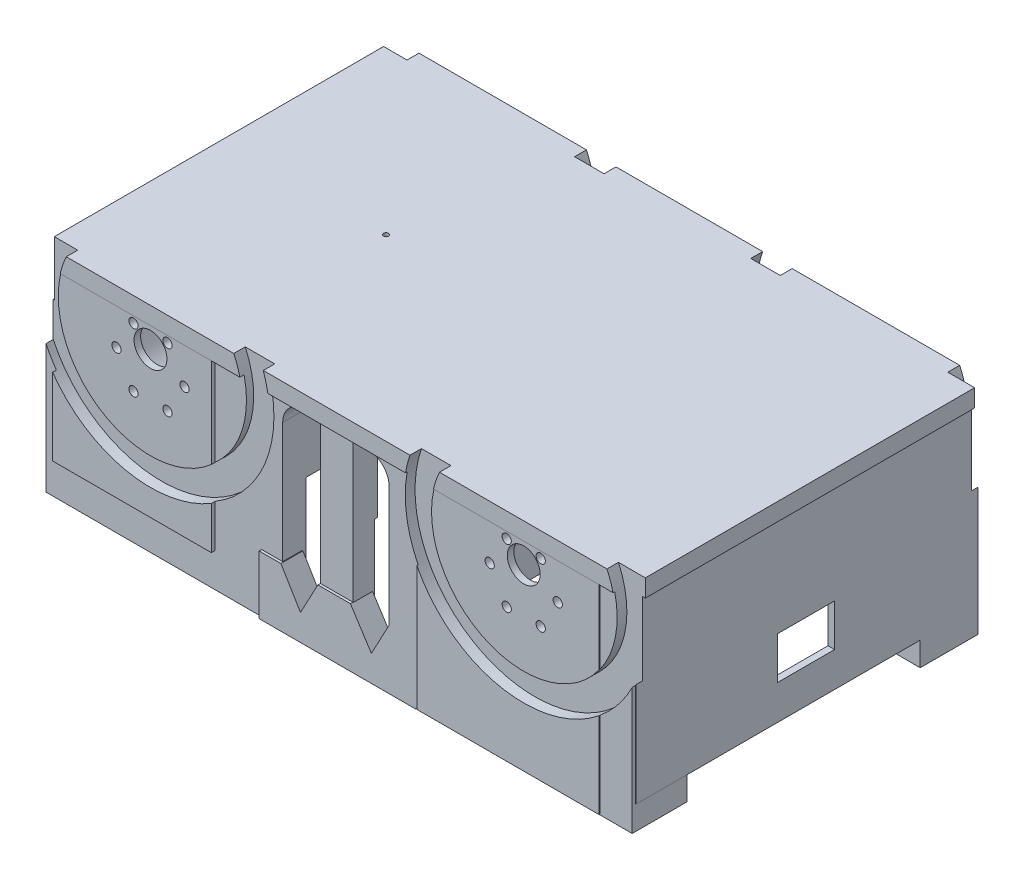
SolidWorks part; units mm, degrees
ref_plane "Front Plane" through (0, 0, 0) normal (0, 0, 1) x (1, 0, 0)
ref_plane "Top Plane" through (0, 0, 0) normal (0, 1, 0) x (1, 0, 0)
ref_plane "Right Plane" through (0, 0, 0) normal (1, 0, 0) x (0, 0, -1)
sketch "MotorHoldersSketch" plane through (0, 0, 0) normal (0, 0, 1) x (1, 0, 0)
  line L0 (0, 0) -> (170, 0) construction
  line L1 (0, 0) -> (0, 23.41) construction
  line L2 (170, 0) -> (170, 23.41) construction
  circle A0 centre (0, 0) radius 23.41
  circle A1 centre (170, 0) radius 23.41
ref_axis "MotorCenterAxis1" through (0, 0, 0) along (0, 0, 1)
ref_axis "MotorCenterAxis2" through (170, 0, 0) along (0, 0, 1)
extrude "MotorHolders" add sketch "MotorHoldersSketch" along normal blind 80 and the other way blind 80
sketch "Sketch3" plane through (0, 0, 0) normal (0, 0, 1) x (1, 0, 0)
  line L1 (1.9406, 21.133) -> (168.3435, 21.133)
  line L2 (1.9406, 21.133) -> (1.9406, 18.3155)
  line L3 (1.9406, 18.3155) -> (168.3435, 18.3155)
  line L4 (168.3435, 21.133) -> (168.3435, 18.3155)
sketch "Sketch4" plane through (0, 0, 0) normal (0, 1, 0) x (1, 0, 0)
  line L1 (221.2811, -76.3794) -> (-41.4939, -76.3794)
  line L2 (221.2811, -76.3794) -> (221.2811, 76.7331)
  line L3 (221.2811, 76.7331) -> (-41.4939, 76.7331)
  line L4 (-41.4939, -76.3794) -> (-41.4939, 76.7331)
extrude "Cut-Extrude1" cut sketch "Sketch4" against normal blind 26
ref_axis "Axis3" through (170, 0, 0) along (0, -1, 0)
sketch3d "ReferencePlanePosition"
  line L0 (170, 0, 0) -> (170, -34.8293, 0)
  line L1 (170, 0, 0) -> (170, -38.994, 0) construction
ref_plane "ReferencePlane" through (170, -34.8293, 0) normal (0, -1, 0) x (-1, 0, 0)
sketch "Sketch6" plane through (170, -34.8293, 0) normal (0, -1, 0) x (-1, 0, 0)
  line L1 (219.5858, 78.949) -> (112.1002, 78.949)
  line L2 (219.5858, 78.949) -> (219.5858, 65.5282)
  line L3 (219.5858, 65.5282) -> (112.1002, 65.5282)
  line L4 (112.1002, 78.949) -> (112.1002, 65.5282)
  line L5 (219.3147, -40.0209) -> (111.499, -40.0209)
  line L6 (219.3147, -40.0209) -> (219.3147, -78.2822)
  line L7 (219.3147, -78.2822) -> (111.499, -78.2822)
  line L8 (111.499, -40.0209) -> (111.499, -78.2822)
  line L9 (61.4891, 77.8627) -> (19.9904, 77.8627)
  line L10 (61.4891, 77.8627) -> (61.4891, 40.7512)
  line L11 (61.4891, 40.7512) -> (19.9904, 40.7512)
  line L12 (19.9904, 77.8627) -> (19.9904, 40.7512)
  line L13 (61.8484, -44.1716) -> (20.0852, -44.1716)
  line L14 (61.8484, -44.1716) -> (61.8484, -79.4437)
  line L15 (61.8484, -79.4437) -> (20.0852, -79.4437)
  line L16 (20.0852, -44.1716) -> (20.0852, -79.4437)
  line L17 (213.765, 73.0364) -> (192.9548, 73.0364)
  line L18 (213.765, 73.0364) -> (213.765, 71.0153)
  line L19 (213.765, 71.0153) -> (192.9548, 71.0153)
  line L20 (192.9548, 73.0364) -> (192.9548, 71.0153)
  line L21 (41.3552, 69.1777) -> (28.5109, 69.1777)
  line L22 (41.3552, 69.1777) -> (41.3552, 50.8413)
  line L23 (41.3552, 50.8413) -> (28.5109, 50.8413)
  line L24 (28.5109, 69.1777) -> (28.5109, 50.8413)
  line L25 (43.3068, -72.8101) -> (32.1723, -72.8101)
  line L26 (43.3068, -72.8101) -> (43.3068, -54.7747)
  line L27 (43.3068, -54.7747) -> (32.1723, -54.7747)
  line L28 (32.1723, -72.8101) -> (32.1723, -54.7747)
  line L29 (211.9411, -70.4881) -> (201.0982, -70.4881)
  line L30 (211.9411, -70.4881) -> (211.9411, -60.1404)
  line L31 (211.9411, -60.1404) -> (201.0982, -60.1404)
  line L32 (201.0982, -70.4881) -> (201.0982, -60.1404)
  line L33 (97.1795, 78.949) -> (79.4162, 78.949)
  line L34 (97.1795, 78.949) -> (97.1795, 67.7632)
  line L35 (97.1795, 67.7632) -> (79.4162, 67.7632)
  line L36 (79.4162, 78.949) -> (79.4162, 67.7632)
  line L37 (58.6711, 51.3198) -> (53.8697, 51.3198)
  line L38 (58.6711, 51.3198) -> (58.6711, 67.7632)
  line L39 (58.6711, 67.7632) -> (53.8697, 67.7632)
  line L40 (53.8697, 51.3198) -> (53.8697, 67.7632)
  line L41 (94.2281, -78.2822) -> (79.4162, -78.2822)
  line L42 (94.2281, -78.2822) -> (94.2281, -67.2515)
  line L43 (94.2281, -67.2515) -> (79.4162, -67.2515)
  line L44 (79.4162, -78.2822) -> (79.4162, -67.2515)
  line L45 (56.3648, -69.8638) -> (51.7107, -69.8638)
  line L46 (56.3648, -69.8638) -> (56.3648, -55.4273)
  line L47 (56.3648, -55.4273) -> (51.7107, -55.4273)
  line L48 (51.7107, -69.8638) -> (51.7107, -55.4273)
  line L49 (-20.7001, -79.4437) -> (-48.8506, -79.4437)
  line L50 (-20.7001, -79.4437) -> (-20.7001, -54.5097)
  line L51 (-20.7001, -54.5097) -> (-48.8506, -54.5097)
  line L52 (-48.8506, -79.4437) -> (-48.8506, -54.5097)
  line L53 (-18.3873, 77.8627) -> (-49.0581, 77.8627)
  line L54 (-18.3873, 77.8627) -> (-18.3873, 51.5325)
  line L55 (-18.3873, 51.5325) -> (-49.0581, 51.5325)
  line L56 (-49.0581, 77.8627) -> (-49.0581, 51.5325)
  line L57 (-41.8141, -72.8101) -> (-31.6362, -72.8101)
  line L58 (-41.8141, -72.8101) -> (-41.8141, -62.9794)
  line L59 (-41.8141, -62.9794) -> (-31.6362, -62.9794)
  line L60 (-31.6362, -72.8101) -> (-31.6362, -62.9794)
  line L61 (-31.6362, 69.1777) -> (-41.5347, 69.1777)
  line L62 (-31.6362, 69.1777) -> (-31.6362, 58.5421)
  line L63 (-31.6362, 58.5421) -> (-41.5347, 58.5421)
  line L64 (-41.5347, 69.1777) -> (-41.5347, 58.5421)
extrude "PowerBankHolders" add sketch "Sketch6" along normal blind 40 and the other way blind 59 separate body
sketch3d "3DSketch3"
  line L0 (170, 0, 0) -> (170, -64.5, 0) construction
ref_plane "Plane2" through (170, -64.5, 0) normal (0, -1, 0) x (-1, 0, 0)
sketch "Sketch7" plane through (170, -64.5, 0) normal (0, -1, 0) x (-1, 0, 0)
  line L1 (-9.5047, -80.801) -> (181.32, -80.801)
  line L2 (-9.5047, -80.801) -> (-9.5047, 73.8662)
  line L3 (-9.5047, 73.8662) -> (181.32, 73.8662)
  line L4 (181.32, -80.801) -> (181.32, 73.8662)
  line L5 (151.8712, -54.3972) -> (26.5361, -54.3972)
  line L6 (151.8712, -54.3972) -> (151.8712, 46.2413)
  line L7 (151.8712, 46.2413) -> (26.5361, 46.2413)
  line L8 (26.5361, -54.3972) -> (26.5361, 46.2413)
ref_point "Point1"
ref_point "Point2"
sketch3d "3DSketch11"
  line L0 (0, 0, -80) -> (170, 0, 80) construction
  point P4 (85, 0, 0)
sketch "MotorHolderExtrudeSketch" plane through (0, 0, 0) normal (0, 0, 1) x (1, 0, 0)
  circle A0 centre (170, 0) radius 20.415
  circle A1 centre (0, 0) radius 20.415
  circle A3 centre (0, 0) radius 23.41 construction
  circle A4 centre (170, 0) radius 23.41 construction
ref_point "TopOfMotors"
ref_plane "TangentToTopOfMotors" through (0, -20.415, 0) normal (0, 1, 0) x (1, 0, 0)
ref_axis "Axis4" through (85, 0, 0) along (0, -1, 0)
ref_plane "BottomOfPowerBankRegion" through (0, -20.425, 0) normal (0, 1, 0) x (1, 0, 0)
ref_point "CenterAtBottomOfPowerBank"
ref_plane "TopOfPowerBankPlane" through (0, -54.425, 0) normal (0, 1, 0) x (1, 0, 0)
sketch "Sketch13" plane through (0, -54.425, 0) normal (0, 1, 0) x (1, 0, 0)
  line L1 (-19.4498, 72.5454) -> (166.1636, 72.5454)
  line L2 (-19.4498, 72.5454) -> (-19.4498, -78.2051)
  line L3 (-19.4498, -78.2051) -> (166.1636, -78.2051)
  line L4 (166.1636, 72.5454) -> (166.1636, -78.2051)
  line L5 (19.3173, -49.583) -> (137.9607, -49.583)
  line L6 (19.3173, -49.583) -> (19.3173, -21.0549)
  line L7 (19.3173, -21.0549) -> (137.9607, -21.0549)
  line L8 (137.9607, -49.583) -> (137.9607, -21.0549)
  line L9 (19.3173, 56.6778) -> (137.9607, 56.6778)
  line L10 (19.3173, 56.6778) -> (19.3173, 36.3234)
  line L11 (19.3173, 36.3234) -> (137.9607, 36.3234)
  line L12 (137.9607, 56.6778) -> (137.9607, 36.3234)
  line L13 (19.3173, 18.3186) -> (137.9607, 18.3186)
  line L14 (19.3173, 18.3186) -> (19.3173, -7.3615)
  line L15 (19.3173, -7.3615) -> (137.9607, -7.3615)
  line L16 (137.9607, 18.3186) -> (137.9607, -7.3615)
sketch "Sketch15" plane through (150.0096, 0, 0) normal (1, 0, 0) x (0, 0, -1)
  line L1 (72.5313, -25.7765) -> (45.7099, -25.7765)
  line L2 (72.5313, -25.7765) -> (72.5313, -24.2242)
  line L3 (72.5313, -24.2242) -> (45.7099, -24.2242)
  line L4 (45.7099, -25.7765) -> (45.7099, -24.2242)
ref_plane "Plane6" through (0, 0, 0) normal (0, 0, 1) x (1, 0, 0)
sketch "MotorGeometry1" plane through (0, 0, 0) normal (0, 0, 1) x (1, 0, 0)
  line L0 (170, 0) -> (170, -13.42)
  line L1 (170, 0) -> (170, -34.8293) construction
  line L2 (170, -13.42) -> (162.25, -13.42) construction
  line L3 (170, -13.42) -> (177.75, -13.42) construction
  line L4 (170, -13.42) -> (170, 7) construction
  line L5 (170, 0) -> (185.5, 0) construction
  line L6 (170, 0) -> (154.5, 0) construction
  line L7 (170, 0) -> (170, 13.42) construction
  line L8 (170, 0) -> (170, 23.41) construction
  line L9 (170, 13.42) -> (177.75, 13.42) construction
  line L10 (170, 13.42) -> (162.25, 13.42)
ref_axis "BoltAxisA" through (185.5, 0, 0) along (0, 0, 1)
ref_axis "BoltAxisB" through (177.75, -13.42, 0) along (0, 0, 1)
ref_axis "BoltAxisC" through (162.25, -13.42, 0) along (0, 0, 1)
ref_axis "BoltAxisD" through (154.5, 0, 0) along (0, 0, 1)
ref_axis "BoltAxisE" through (162.25, 13.42, 0) along (0, 0, 1)
ref_axis "BoltAxisF" through (177.75, 13.42, 0) along (0, 0, 1)
ref_point "Point6"
ref_point "Point7"
ref_point "Point8"
ref_point "Point9"
ref_point "Point10"
ref_point "Point11"
ref_point "Point12"
ref_point "Point13"
ref_point "Point14"
ref_point "Point15"
ref_point "Point16"
ref_point "Point17"
ref_plane "Plane7" through (0, 0, 0) normal (0, 0, 1) x (1, 0, 0)
sketch "MotorGeometry2" plane through (0, 0, 0) normal (0, 0, 1) x (1, 0, 0)
  line L0 (0, 0) -> (0, -13.42) construction
  line L1 (0, -13.42) -> (7.75, -13.42) construction
  line L2 (0, -13.42) -> (-7.75, -13.42) construction
  line L3 (0, 0) -> (0, 13.42)
  line L4 (0, -13.42) -> (0, 7) construction
  line L5 (0, 13.42) -> (7.75, 13.42) construction
  line L6 (0, 13.42) -> (-7.75, 13.42) construction
  line L7 (0, 0) -> (15.5, 0) construction
  line L8 (0, 0) -> (-15.5, 0) construction
  line L9 (0, 0) -> (0, 23.41) construction
ref_axis "Axis11" through (15.5, 0, 0) along (0, 0, 1)
ref_axis "Axis12" through (7.75, 13.42, 0) along (0, 0, 1)
ref_axis "Axis13" through (-7.75, 13.42, 0) along (0, 0, 1)
ref_axis "Axis14" through (-15.5, 0, 0) along (0, 0, 1)
ref_axis "Axis15" through (-7.75, -13.42, 0) along (0, 0, 1)
ref_axis "Axis16" through (7.75, -13.42, 0) along (0, 0, 1)
ref_point "Point18"
ref_point "Point19"
ref_point "Point20"
ref_point "Point21"
ref_point "Point22"
ref_point "Point23"
ref_point "Point24"
ref_point "Point25"
ref_point "Point26"
ref_point "Point27"
ref_point "Point28"
ref_point "Point29"
ref_plane "BottomPlane" through (0, 19.575, 0) normal (0, 1, 0) x (1, 0, 0)
ref_axis "OutputShaftReference1" through (0, 7, 0) along (0, 0, 1)
ref_point "Point35"
ref_axis "OutputShaftReference2" through (170, 7, 0) along (0, 0, 1)
sketch "Sketch21" plane through (0, 19.575, 0) normal (0, 1, 0) x (1, 0, 0)
  line L0 (219.6842, -79.5488) -> (-50.341, -79.5488) construction
  line L1 (-50.341, -79.5488) -> (-50.341, 79.7899) construction
  line L2 (-50.341, 79.7899) -> (219.6842, 79.7899) construction
  line L3 (219.6842, 79.7899) -> (219.6842, -79.5488) construction
  circle A0 centre (85, 0) radius 156.3953
extrude "BottomPlate" add sketch "Sketch21" along normal blind 5 and the other way blind 3
ref_plane "HoleReferencePlane1" through (0, 0, 80) normal (0, 0, 1) x (1, 0, 0)
ref_point "OutputShaftPosition3"
ref_point "OutputShaftPosition1"
sketch "Sketch23" plane through (0, 0, 80) normal (0, 0, 1) x (1, 0, 0)
  line L1 (27.7411, -59.3229) -> (-44.5901, -59.3229)
  line L2 (27.7411, -59.3229) -> (27.7411, 21.8402)
  line L3 (27.7411, 21.8402) -> (-44.5901, 21.8402)
  line L4 (-44.5901, -59.3229) -> (-44.5901, 21.8402)
  line L5 (121.3218, 21.8402) -> (204.258, 21.8402)
  line L6 (121.3218, 21.8402) -> (121.3218, -74.371)
  line L7 (121.3218, -74.371) -> (204.258, -74.371)
  line L8 (204.258, 21.8402) -> (204.258, -74.371)
extrude "MotorMountingSupport1" add sketch "Sketch23" against normal blind 6
ref_plane "HoleReferencePlane2" through (0, 0, -80) normal (0, 0, -1) x (-1, 0, 0)
ref_point "OutputShaftPosition4"
ref_point "OutputShaftPosition2"
sketch "Sketch24" plane through (0, 0, -80) normal (0, 0, -1) x (-1, 0, 0)
  line L1 (-202.1905, -75.2023) -> (-123.8485, -75.2023)
  line L2 (-202.1905, -75.2023) -> (-202.1905, 19.2374)
  line L3 (-202.1905, 19.2374) -> (-123.8485, 19.2374)
  line L4 (-123.8485, -75.2023) -> (-123.8485, 19.2374)
  line L5 (-24.3642, -64.1521) -> (29.5505, -64.1521)
  line L6 (-24.3642, -64.1521) -> (-24.3642, 22.5226)
  line L7 (-24.3642, 22.5226) -> (29.5505, 22.5226)
  line L8 (29.5505, -64.1521) -> (29.5505, 22.5226)
extrude "MotorMountingSuppor2" add sketch "Sketch24" against normal blind 6
sketch "Sketch17" plane through (0, 0, 80) normal (0, 0, 1) x (1, 0, 0)
  circle A0 centre (185.5, 0) radius 2.1
  circle A1 centre (177.75, -13.42) radius 2.1
  circle A2 centre (162.25, -13.42) radius 2.1
  circle A3 centre (154.5, 0) radius 2.1
  circle A4 centre (162.25, 13.42) radius 2.1
  circle A5 centre (177.75, 13.42) radius 2.1
  circle A6 centre (170, 7) radius 7.5
extrude "MotorHoles1" cut sketch "Sketch17" against normal blind 31.5
sketch "Sketch19" plane through (0, 0, -80) normal (0, 0, -1) x (-1, 0, 0)
  circle A0 centre (-185.5, 0) radius 2.1
  circle A1 centre (-177.75, -13.42) radius 2.1
  circle A2 centre (-162.25, -13.42) radius 2.1
  circle A3 centre (-154.5, 0) radius 2.1
  circle A4 centre (-162.25, 13.42) radius 2.1
  circle A5 centre (-177.75, 13.42) radius 2.1
  circle A6 centre (-170, 7) radius 7.5
sketch "BoltHolesSketch3" plane through (0, 0, 80) normal (0, 0, 1) x (1, 0, 0)
  circle A0 centre (7.75, -13.42) radius 2.1
  circle A1 centre (15.5, 0) radius 2.1
  circle A2 centre (7.75, 13.42) radius 2.1
  circle A3 centre (-7.75, 13.42) radius 2.1
  circle A4 centre (-15.5, 0) radius 2.1
  circle A5 centre (-7.75, -13.42) radius 2.1
  circle A6 centre (0, 7) radius 7.5
extrude "Cut-Extrude4" cut sketch "Sketch19" against normal blind 30
extrude "MotorHoles3" cut sketch "BoltHolesSketch3" against normal blind 31.5
sketch "BoltHolesSketch4" plane through (0, 0, -80) normal (0, 0, -1) x (-1, 0, 0)
  circle A0 centre (-15.5, 0) radius 2.1
  circle A1 centre (-7.75, 13.42) radius 2.1
  circle A2 centre (7.75, 13.42) radius 2.1
  circle A3 centre (15.5, 0) radius 2.1
  circle A4 centre (7.75, -13.42) radius 2.1
  circle A5 centre (-7.75, -13.42) radius 2.1
  circle A6 centre (0, 7) radius 7.5
extrude "MotorHoles4" cut sketch "BoltHolesSketch4" against normal blind 15
ref_plane "Front" through (219.0581, 0, 0) normal (1, 0, 0) x (0, 0, -1)
sketch "Sketch29" plane through (219.0581, 0, 0) normal (1, 0, 0) x (0, 0, -1)
  line L1 (76.6955, -63.9254) -> (-77.9397, -63.9254)
  line L2 (76.6955, -63.9254) -> (76.6955, 20.2062)
  line L3 (76.6955, 20.2062) -> (-77.9397, 20.2062)
  line L4 (-77.9397, -63.9254) -> (-77.9397, 20.2062)
  line L5 (-13.4507, -48.1531) -> (12.5493, -48.1531)
  line L6 (-13.4507, -48.1531) -> (-13.4507, -28.9404)
  line L7 (-13.4507, -28.9404) -> (12.5493, -28.9404)
  line L8 (12.5493, -48.1531) -> (12.5493, -28.9404)
extrude "Boss-Extrude8" add sketch "Sketch29" against normal blind 3
ref_plane "RaspberryPiBasePlane" through (0, 16.575, 0) normal (0, -1, 0) x (-1, 0, 0)
sketch "Sketch27" plane through (0, 16.575, 0) normal (0, -1, 0) x (-1, 0, 0)
  line L1 (31.6337, 64.5517) -> (-194.8264, 64.5517)
  line L2 (31.6337, 64.5517) -> (31.6337, -65.4335)
  line L3 (31.6337, -65.4335) -> (-194.8264, -65.4335)
  line L4 (-194.8264, 64.5517) -> (-194.8264, -65.4335)
extrude "Boss-Extrude6" add sketch "Sketch27" against normal blind 3
ref_plane "Plane12" through (0, -74.8293, 0) normal (0, -1, 0) x (-1, 0, 0)
sketch "Sketch28" plane through (0, -74.8293, 0) normal (0, -1, 0) x (-1, 0, 0)
  line L1 (-189.3897, -97.3973) -> (-123.0026, -97.3973)
  line L2 (-189.3897, -97.3973) -> (-189.3897, 96.7192)
  line L3 (-189.3897, 96.7192) -> (-123.0026, 96.7192)
  line L4 (-123.0026, -97.3973) -> (-123.0026, 96.7192)
sketch "Sketch40" plane through (0, 16.575, 0) normal (0, -1, 0) x (1, 0, 0)
  line L1 (-49.5858, -65.5282) -> (-15.7443, -65.5282)
  line L2 (-49.5858, -65.5282) -> (-49.5858, -33.9964)
  line L3 (-49.5858, -33.9964) -> (-15.7443, -33.9964)
  line L4 (-15.7443, -65.5282) -> (-15.7443, -33.9964)
extrude "Boss-Extrude11" add sketch "Sketch40" along normal blind 40
fillet "Fillet2" radius 15 1 edges at (-33.0588, 16.575, -33.9964) type face fillet first side face at (-28.7089, -2.1691, -33.9964) second side face at (85, 16.575, 156.3953)
fillet "Fillet3" radius 15 1 edges at (-32.6651, -23.425, -65.5282) type face fillet first side face at (-5.65, -13.42, -65.5282) second side face at (-32.6651, -23.425, -49.7623)
sketch "Sketch11" plane through (0, -20.425, 0) normal (0, 1, 0) x (1, 0, 0)
  line L0 (-34.2162, 4.2922) -> (204.2162, -4.2922) construction
  line L5 (-34.2162, -64.7581) -> (-34.2162, 73.3425)
  line L6 (204.2162, 63.611) -> (204.2162, -72.1954)
  line L7 (204.2162, -72.1954) -> (-34.2162, -64.7581)
  line L8 (204.2162, 63.611) -> (-34.2162, 73.3425)
  circle A0 centre (85, 0) radius 104 construction
extrude "PowerBankCut" cut sketch "Sketch11" against normal up to surface (54.4043 mm away) up to face at (204.7754, -74.8293, 66.9767)
extrude "MotorHolderCut" cut sketch "MotorHolderExtrudeSketch" against normal blind 77 and the other way blind 77
sketch "Sketch31" plane through (219.0581, 0, 0) normal (1, 0, 0) x (0, 0, -1)
  line L0 (49.4417, -6.1927) -> (49.4417, -19.3739)
  line L1 (49.4417, -19.3739) -> (42.9342, -21.6341)
  line L2 (42.9342, -21.6341) -> (40.0618, -21.6341)
  line L3 (40.0618, -21.6341) -> (37.7863, -19.3586)
  line L4 (37.7863, -19.3586) -> (37.7863, -15.3813)
  line L5 (37.7863, -15.3813) -> (40.0618, -13.1059)
  line L6 (40.0618, -13.1059) -> (37.7863, -6.5545)
  line L7 (37.7863, -6.5545) -> (41.498, -6.5545)
  line L8 (41.498, -6.5545) -> (43.4004, -12.0319)
  line L9 (43.4004, -12.0319) -> (46.389, -12.0319)
  line L10 (46.389, -12.0319) -> (46.389, -6.5545)
  line L11 (46.389, -6.5545) -> (49.4417, -6.1927)
  line L12 (33.0193, -21.6341) -> (33.0193, -9.8302)
  line L13 (33.0193, -9.8302) -> (30.5402, -7.3511)
  line L14 (30.5402, -7.3511) -> (25.7203, -7.3511)
  line L15 (25.7203, -7.3511) -> (23.2412, -9.8302)
  line L16 (23.2412, -9.8302) -> (23.2412, -21.6341)
  line L17 (23.2412, -21.6341) -> (25.7203, -21.6341)
  line L18 (25.7203, -21.6341) -> (25.7203, -10.7454)
  line L19 (25.7203, -10.7454) -> (30.5402, -10.7454)
  line L20 (30.5402, -10.7454) -> (30.5402, -21.6341)
  line L21 (30.5402, -21.6341) -> (33.0193, -21.6341)
  line L22 (19.7226, -8.5907) -> (19.7226, -21.6341)
  line L23 (19.7226, -21.6341) -> (13.8207, -15.7322)
  line L24 (13.8207, -15.7322) -> (13.8207, -21.6341)
  line L25 (13.8207, -21.6341) -> (10.7708, -21.6341)
  line L26 (10.7708, -21.6341) -> (10.7708, -8.5907)
  line L27 (10.7708, -8.5907) -> (16.7716, -14.5915)
  line L28 (16.7716, -14.5915) -> (16.7716, -8.5907)
  line L29 (16.7716, -8.5907) -> (19.7226, -8.5907)
  line L30 (7.3891, -8.5907) -> (7.3891, -21.6341)
  line L31 (7.3891, -21.6341) -> (3.7282, -21.6341)
  line L32 (3.7282, -21.6341) -> (1.3209, -17.37)
  line L33 (1.3209, -17.37) -> (-1.2519, -21.6341)
  line L34 (-1.2519, -21.6341) -> (-3.6554, -21.6341)
  line L35 (-3.6554, -21.6341) -> (-4.6916, -8.5907)
  line L36 (-4.6916, -8.5907) -> (-2.4537, -8.5907)
  line L37 (-2.4537, -8.5907) -> (0.0345, -15.7545)
  line L38 (0.0345, -15.7545) -> (1.3209, -13.6224)
  line L39 (1.3209, -13.6224) -> (4.8544, -15.7545)
  line L40 (4.8544, -15.7545) -> (4.8544, -8.5907)
  line L41 (4.8544, -8.5907) -> (7.3891, -8.5907)
  line L42 (-7.6823, -21.6341) -> (-10.9875, -15.7545)
  line L43 (-10.9875, -15.7545) -> (-10.9875, -8.5907)
  line L44 (-10.9875, -8.5907) -> (-15.3102, -8.5907)
  line L45 (-15.3102, -8.5907) -> (-15.3102, -15.7545)
  line L46 (-15.3102, -15.7545) -> (-19.2695, -21.6341)
  line L47 (-19.2695, -21.6341) -> (-15.3102, -21.6341)
  line L48 (-15.3102, -21.6341) -> (-13.1489, -18.4245)
  line L49 (-13.1489, -18.4245) -> (-10.9875, -22.2693)
  line L50 (-10.9875, -22.2693) -> (-7.6823, -21.6341)
  line L51 (46.389, -17.8857) -> (46.389, -14.5915)
  line L52 (46.389, -14.5915) -> (41.498, -14.5915)
  line L53 (41.498, -14.5915) -> (39.5067, -16.2541)
  line L54 (39.5067, -16.2541) -> (41.5656, -18.7201)
  line L55 (41.5656, -18.7201) -> (46.389, -17.8857)
  line L56 (-22.571, -8.5907) -> (-22.0989, -21.6341)
  line L57 (-22.0989, -21.6341) -> (-26.4915, -21.6341)
  line L58 (-26.4915, -21.6341) -> (-29.9116, -19.3586)
  line L59 (-29.9116, -19.3586) -> (-30.636, -15.7545)
  line L60 (-30.636, -15.7545) -> (-27.4135, -14.1052)
  line L61 (-27.4135, -14.1052) -> (-30.636, -8.5907)
  line L62 (-30.636, -8.5907) -> (-27.4135, -8.5907)
  line L63 (-27.4135, -8.5907) -> (-25.3987, -14.1052)
  line L64 (-25.3987, -14.1052) -> (-24.2952, -14.1052)
  line L65 (-24.2952, -14.1052) -> (-24.4948, -8.5907)
  line L66 (-24.4948, -8.5907) -> (-22.571, -8.5907)
  line L67 (-35.0099, -8.5907) -> (-38.6395, -8.5907)
  line L68 (-38.6395, -8.5907) -> (-41.5241, -13.6224)
  line L69 (-41.5241, -13.6224) -> (-41.5241, -18.4245)
  line L70 (-41.5241, -18.4245) -> (-38.6395, -21.3091)
  line L71 (-38.6395, -21.3091) -> (-35.0099, -21.3091)
  line L72 (-35.0099, -21.3091) -> (-32.4978, -18.797)
  line L73 (-32.4978, -18.797) -> (-32.4978, -14.1052)
  line L74 (-32.4978, -14.1052) -> (-35.0099, -8.5907)
  line L75 (-44.0593, -21.3091) -> (-44.0593, -8.5907)
  line L76 (-44.0593, -8.5907) -> (-49.4499, -8.5907)
  line L77 (-49.4499, -8.5907) -> (-52.2269, -11.3677)
  line L78 (-52.2269, -11.3677) -> (-52.2269, -14.1052)
  line L79 (-52.2269, -14.1052) -> (-50.5777, -15.7545)
  line L80 (-50.5777, -15.7545) -> (-52.2269, -17.4037)
  line L81 (-52.2269, -17.4037) -> (-52.2269, -19.3586)
  line L82 (-52.2269, -19.3586) -> (-49.4499, -21.3091)
  line L83 (-49.4499, -21.3091) -> (-44.0593, -21.3091)
  line L84 (-57.7977, -21.3091) -> (-55.6011, -19.1125)
  line L85 (-55.6011, -19.1125) -> (-55.6011, -10.7454)
  line L86 (-55.6011, -10.7454) -> (-59.2637, -8.5907)
  line L87 (-59.2637, -8.5907) -> (-61.7818, -8.5907)
  line L88 (-61.7818, -8.5907) -> (-63.9365, -10.7454)
  line L89 (-63.9365, -10.7454) -> (-63.9365, -19.1125)
  line L90 (-63.9365, -19.1125) -> (-61.7818, -21.2672)
  line L91 (-61.7818, -21.2672) -> (-57.7977, -21.3091)
  line L92 (-66.7918, -21.2672) -> (-74.8705, -21.2672)
  line L93 (-74.8705, -21.2672) -> (-74.8705, -19.1125)
  line L94 (-74.8705, -19.1125) -> (-72.2665, -19.1125)
  line L95 (-72.2665, -19.1125) -> (-72.2665, -8.5907)
  line L96 (-72.2665, -8.5907) -> (-69.9977, -8.5907)
  line L97 (-69.9977, -8.5907) -> (-69.9977, -19.1125)
  line L98 (-69.9977, -19.1125) -> (-66.7918, -19.1125)
  line L99 (-66.7918, -19.1125) -> (-66.7918, -21.2672)
  line L100 (-36.1114, -18.797) -> (-34.7181, -17.4037)
  line L101 (-34.7181, -17.4037) -> (-34.7181, -13.1059)
  line L102 (-34.7181, -13.1059) -> (-36.6627, -11.1613)
  line L103 (-36.6627, -11.1613) -> (-37.8659, -11.1613)
  line L104 (-37.8659, -11.1613) -> (-39.3107, -13.1059)
  line L105 (-39.3107, -13.1059) -> (-39.5155, -16.8544)
  line L106 (-39.5155, -16.8544) -> (-38.25, -18.7201)
  line L107 (-38.25, -18.7201) -> (-36.1114, -18.797)
  line L108 (-46.2436, -16.8544) -> (-48.9032, -16.8544)
  line L109 (-48.9032, -16.8544) -> (-49.4499, -18.4245)
  line L110 (-49.4499, -18.4245) -> (-48.0836, -19.3586)
  line L111 (-48.0836, -19.3586) -> (-46.2436, -19.3586)
  line L112 (-46.2436, -19.3586) -> (-46.2436, -16.8544)
  line L113 (-45.9206, -14.5915) -> (-45.9206, -11.1613)
  line L114 (-45.9206, -11.1613) -> (-49.2105, -10.7454)
  line L115 (-49.2105, -10.7454) -> (-50.1756, -12.8764)
  line L116 (-50.1756, -12.8764) -> (-48.5891, -14.5915)
  line L117 (-48.5891, -14.5915) -> (-45.9206, -14.5915)
  line L118 (-58.5672, -18.7201) -> (-57.7977, -17.4037)
  line L119 (-57.7977, -17.4037) -> (-57.7977, -11.7636)
  line L120 (-57.7977, -11.7636) -> (-59.6573, -10.7454)
  line L121 (-59.6573, -10.7454) -> (-60.8144, -10.7454)
  line L122 (-60.8144, -10.7454) -> (-62.101, -12.0319)
  line L123 (-62.101, -12.0319) -> (-61.7818, -17.4037)
  line L124 (-61.7818, -17.4037) -> (-60.8144, -18.7201)
  line L125 (-60.8144, -18.7201) -> (-58.5672, -18.7201)
  line L126 (-24.2952, -19.3586) -> (-24.2952, -16.2541)
  line L127 (-24.2952, -16.2541) -> (-26.4915, -16.2541)
  line L128 (-26.4915, -16.2541) -> (-27.4135, -17.1761)
  line L129 (-27.4135, -17.1761) -> (-27.4135, -18.4245)
  line L130 (-27.4135, -18.4245) -> (-26.3339, -19.5041)
  line L131 (-26.3339, -19.5041) -> (-24.2952, -19.3586)
sketch "Sketch32" plane through (0, 19.575, 0) normal (0, 1, 0) x (1, 0, 0)
  line L1 (-48.8137, 80.4301) -> (220.392, 80.4301)
  line L2 (-48.8137, 80.4301) -> (-48.8137, -80.215)
  line L3 (-48.8137, -80.215) -> (220.392, -80.215)
  line L4 (220.392, 80.4301) -> (220.392, -80.215)
  line L5 (283.5566, -218.7268) -> (-136.4889, -218.7268)
  line L8 (-136.4889, -218.7268) -> (-136.4889, 206.3198)
  line L10 (283.5566, 206.3198) -> (283.5566, -218.7268)
  line L13 (283.5566, 206.3198) -> (-136.4889, 206.3198)
extrude "BaseDefiningCut" cut sketch "Sketch32" along normal blind 20 and the other way blind 20
sketch "Sketch39" plane through (0, 16.575, 0) normal (0, -1, 0) x (1, 0, 0)
  line L1 (-48.8137, -65.5282) -> (-16.0867, -65.5282)
  line L2 (-48.8137, -65.5282) -> (-48.8137, -46.28)
  line L3 (-48.8137, -46.28) -> (-16.0867, -46.28)
  line L4 (-16.0867, -65.5282) -> (-16.0867, -46.28)
sketch "Sketch35" plane through (0, 0, -80.4301) normal (0, 0, -1) x (-1, 0, 0)
  line L0 (69.0502, 16.3777) -> (-36.4474, 27.6206)
  line L1 (-36.4474, 27.6206) -> (71.6404, 26.1593)
  line L2 (69.0502, 16.3777) -> (71.6404, 26.1593)
  line L3 (-223.8844, 30.8145) -> (-223.8844, 17.5678)
  line L4 (-223.8844, 17.5678) -> (-116.0163, 30.8145)
  line L5 (-116.0163, 30.8145) -> (-223.8844, 30.8145)
sketch "Sketch36" plane through (-49.3147, 0, 0) normal (-1, 0, 0) x (0, 0, 1)
  line L0 (40.0209, -74.8293) -> (40.0209, -38.3689) construction
  line L1 (49.3822, -38.3689) -> (78.2822, -38.3689) construction
  line L2 (40.0209, -38.3689) -> (40.0209, -74.8293) construction
  line L3 (78.2822, -0.425) -> (78.2822, -74.8293) construction
  circle A1 centre (49.3822, -38.3689) radius 7.7902
extrude "Cut-Extrude6" cut sketch "Sketch36" against normal blind 40
sketch "Sketch37" plane through (0, -20.425, 0) normal (0, -1, 0) x (1, 0, 0)
  line L1 (144.416, -35.6729) -> (89.0759, -35.6729)
  line L2 (144.416, -35.6729) -> (144.416, -65.4438)
  line L3 (144.416, -65.4438) -> (89.0759, -65.4438)
  line L4 (89.0759, -35.6729) -> (89.0759, -65.4438)
extrude "Cut-Extrude7" cut sketch "Sketch37" against normal blind 36
sketch "Sketch38" plane through (0, 16.575, 0) normal (0, -1, 0) x (1, 0, 0)
  line L0 (25.9964, 80.215) -> (25.9964, -1.3165) construction
  line L1 (-48.8137, 80.215) -> (219.2574, 80.215) construction
  circle A0 centre (25.9964, -1.3165) radius 1.1452
extrude "Cut-Extrude8" cut sketch "Sketch38" against normal blind 10
sketch "Sketch41" plane through (0, 0, 80) normal (0, 0, 1) x (1, 0, 0)
  circle A0 centre (0, 7) radius 42
  circle A1 centre (0, 7) radius 54.5
extrude "SpaceForWheel1" cut sketch "Sketch41" against normal blind 5 and the other way blind 10
sketch "Sketch42" plane through (0, 0, 80) normal (0, 0, 1) x (1, 0, 0)
  circle A0 centre (170, 7) radius 42
  circle A1 centre (170, 7) radius 54.5
extrude "Cut-Extrude10" cut sketch "Sketch42" against normal blind 5 and the other way blind 10
sketch "Sketch43" plane through (0, 0, -80) normal (0, 0, -1) x (-1, 0, 0)
  circle A0 centre (-170, 7) radius 42
  circle A1 centre (-170, 7) radius 54.5
extrude "Cut-Extrude11" cut sketch "Sketch43" against normal blind 5 and the other way blind 10
sketch "Sketch44" plane through (0, 0, -80) normal (0, 0, -1) x (-1, 0, 0)
  circle A0 centre (0, 7) radius 42
  circle A1 centre (0, 7) radius 54.5
extrude "Cut-Extrude12" cut sketch "Sketch44" against normal blind 5 and the other way blind 10
sketch "Sketch45" plane through (-48.8137, 0, 0) normal (-1, 0, 0) x (0, 0, 1)
  line L0 (-75, 24.575) -> (75, 24.575) construction
  line L1 (-72.1063, 24.575) -> (42.0312, 24.575)
  line L2 (-72.1063, 24.575) -> (-72.1063, -74.1222)
  line L3 (-72.1063, -74.1222) -> (42.0312, -74.1222)
  line L4 (42.0312, 24.575) -> (42.0312, -74.1222)
extrude "BackPlate" add sketch "Sketch45" against normal blind 2
sketch "Sketch46" plane through (0, -74.8293, 0) normal (0, -1, 0) x (1, 0, 0)
  line L1 (97.1427, -74.9256) -> (213.5256, -74.9256)
  line L2 (97.1427, -74.9256) -> (97.1427, -71.5234)
  line L3 (97.1427, -71.5234) -> (213.5256, -71.5234)
  line L4 (213.5256, -74.9256) -> (213.5256, -71.5234)
  line L5 (97.1427, 72.8226) -> (213.5256, 72.8226)
  line L6 (97.1427, 72.8226) -> (97.1427, 77.4687)
  line L7 (97.1427, 77.4687) -> (213.5256, 77.4687)
  line L8 (213.5256, 72.8226) -> (213.5256, 77.4687)
fillet "Fillet8" radius 10 1 edges at (57.8998, 16.575, -72.2386) type face fillet first side face at (57.8998, -26.2264, -71.3533) second side face at (25.9964, 16.575, -2.4617)
fillet "Fillet9" radius 10 1 edges at (108.5109, 16.575, -59.3069) type face fillet first side face at (108.5109, -15.7761, -62.8937) second side face at (25.9964, 16.575, -2.4617)
fillet "Fillet10" radius 10 1 edges at (108.1516, 16.575, 61.8076) type face fillet first side face at (108.1516, -26.2264, 64.2714) second side face at (25.9964, 16.575, -2.4617)
sketch "Sketch49" plane through (0, 0, 80) normal (0, 0, 1) x (1, 0, 0)
  line L0 (27.7411, -24.5346) -> (27.7411, 16.575) construction
  circle A0 centre (27.7411, 12.953) radius 3.5831
fillet "Fillet11" radius 10 1 edges at (58.501, 16.575, 59.1515) type face fillet first side face at (58.501, -26.2264, 61.9844) second side face at (25.9964, 16.575, -2.4617)
sketch "Sketch50" plane through (0, -74.8293, 0) normal (0, -1, 0) x (1, 0, 0)
  line L1 (-49.3147, 40.0209) -> (-40.7689, 40.0209)
  line L2 (-49.3147, 40.0209) -> (-49.3147, 52.7795)
  line L3 (-49.3147, 52.7795) -> (-40.7689, 52.7795)
  line L4 (-40.7689, 40.0209) -> (-40.7689, 52.7795)
  line L5 (-49.5858, -65.5282) -> (-35.8777, -65.5282)
  line L6 (-49.5858, -65.5282) -> (-49.5858, -77.7316)
  line L7 (-49.5858, -77.7316) -> (-35.8777, -77.7316)
  line L8 (-35.8777, -65.5282) -> (-35.8777, -77.7316)
sketch "Sketch51" plane through (0, 0, 79.4437) normal (0, 0, 1) x (1, 0, 0)
  line L0 (108.1516, -47.9804) -> (100.047, -63.1792)
  line L1 (108.1516, 6.575) -> (108.1516, -74.8293) construction
  line L2 (100.047, -63.1792) -> (90.5163, -48.3368)
  line L3 (90.5163, -48.3368) -> (75.6762, -48.3368)
  line L4 (75.6762, -48.3368) -> (67.7615, -63.1792)
  line L5 (67.7615, -63.1792) -> (58.8398, -48.3368)
  line L6 (58.8398, -48.3368) -> (48.9291, -48.3368)
  line L7 (48.9291, -48.3368) -> (48.9291, -75.0407)
  line L8 (48.9291, -75.0407) -> (120.2514, -75.0407)
  line L9 (120.2514, -75.0407) -> (120.2514, -47.9804)
  line L10 (120.2514, -47.9804) -> (108.1516, -47.9804)
extrude "Boss-Extrude12" add sketch "Sketch51" against normal blind 10
sketch "Sketch53" plane through (0, 0, -77.8627) normal (0, 0, -1) x (-1, 0, 0)
  line L1 (-57.7992, -55.7616) -> (-64.6668, -65.1072)
  line L2 (-64.6668, -65.1072) -> (-72.7541, -55.7616)
  line L3 (-72.7541, -55.7616) -> (-90.6554, -55.7616)
  line L4 (-90.6554, -55.7616) -> (-98.6681, -65.1072)
  line L5 (-98.6681, -65.1072) -> (-108.5109, -55.7616)
  line L6 (-108.5109, 6.575) -> (-108.5109, -74.8293) construction
  line L7 (-108.5109, -55.7616) -> (-123.8485, -55.7616)
  line L8 (-123.8485, -21.9878) -> (-123.8485, -74.8293) construction
  line L9 (-123.8485, -55.7616) -> (-123.8485, -74.8293)
  line L10 (-123.8485, -74.8293) -> (-52.4383, -74.8293)
  line L11 (-52.4383, -74.8293) -> (-52.4383, -55.7616)
  line L12 (-52.4383, -55.7616) -> (-57.7992, -55.7616)
extrude "Boss-Extrude13" add sketch "Sketch53" against normal blind 9
